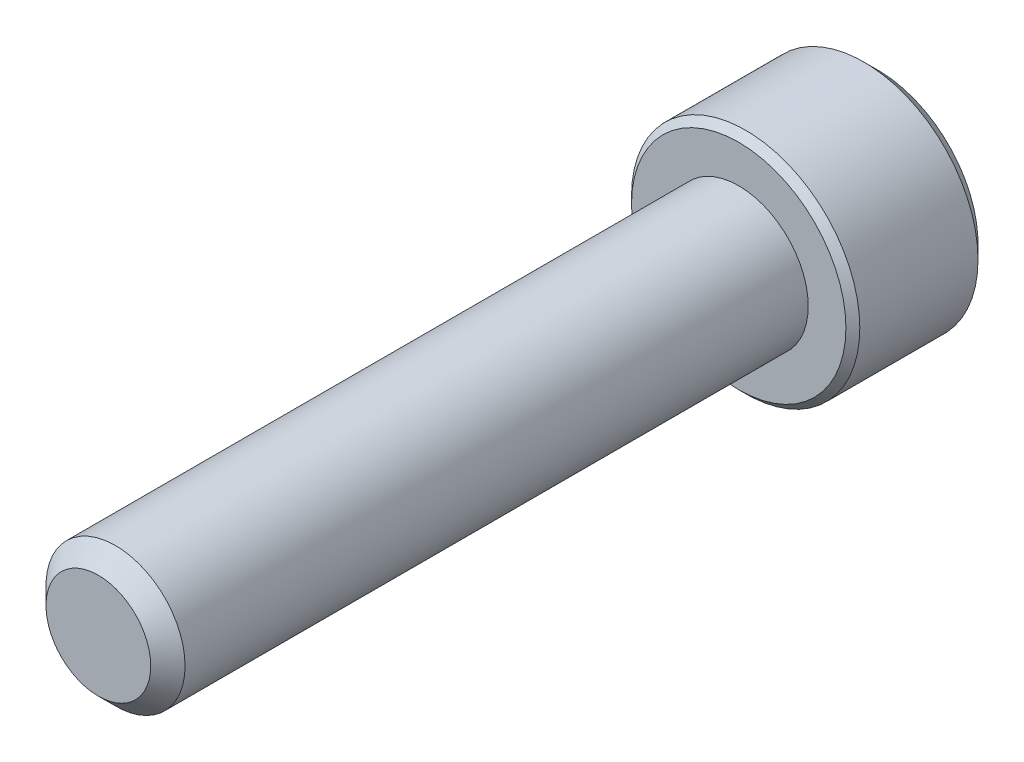
SolidWorks part; units mm, degrees
ref_plane "Front Plane" through (0, 0, 0) normal (0, 0, 1) x (1, 0, 0)
ref_plane "Top Plane" through (0, 0, 0) normal (0, 1, 0) x (1, 0, 0)
ref_plane "Right Plane" through (0, 0, 0) normal (1, 0, 0) x (0, 0, -1)
sketch "Sketch1" plane through (0, 0, 0) normal (0, 0, 1) x (1, 0, 0)
  line L0 (0, 2.413) -> (0, -2.413) construction
  circle A0 centre (0, 0) radius 2.413
  dimension "OD" = 4.826
extrude "Extrude1" add sketch "Sketch1" against normal blind 22.225
sketch "Sketch2" plane through (0, 0, 0) normal (0, 0, 1) x (1, 0, 0)
  circle A0 centre (0, 0) radius 2.413 construction
  circle A1 centre (0, 0) radius 2.413
curve "Helix/Spiral1" pitch 0.7937 height 23.0188 turns 29 parameters "pitch"=0.7937
chamfer "Chamfer3" distance 0.5953 angle 45 1 edges at (2.413, 0, 0)
sketch "Sketch3" plane through (0, 0, 0) normal (1, 0, 0) x (0, 0, -1)
  line L0 (-0.6945, 2.413) -> (-0.3969, 1.8974)
  line L1 (-0.3969, 1.8974) -> (-0.2977, 1.8974)
  line L2 (-0.2977, 1.8974) -> (0, 2.413)
  line L3 (-0.6945, 2.413) -> (0, 2.413)
  line L4 (-0.3473, 2.413) -> (-0.3473, 1.8974) construction
  line L5 (-0.5457, 2.1552) -> (-0.1488, 2.1552) construction
  line L6 (0, 2.413) -> (0, -2.413) construction
  dimension "D1" = 0.0992
  dimension "D2" = 0.3969
  dimension "D3" = 60
sweep "Cut-Sweep1" [suppressed] cut profiles "Sketch3" path "Helix/Spiral1"
sketch "Sketch6" plane through (0, 0, -22.225) normal (0, 0, -1) x (-1, 0, 0)
  circle A0 centre (0, 0) radius 3.9624
  dimension "head dia" = 7.9248
extrude "Extrude2" add sketch "Sketch6" along normal blind 4.826
sketch "Sketch7" plane through (0, 0, -27.051) normal (0, 0, -1) x (-1, 0, 0)
  line L1 (0, 2.2914) -> (-1.9844, 1.1457)
  line L2 (-1.9844, 1.1457) -> (-1.9844, -1.1457)
  line L3 (-1.9844, -1.1457) -> (0, -2.2914)
  line L4 (0, -2.2914) -> (1.9844, -1.1457)
  line L5 (1.9844, -1.1457) -> (1.9844, 1.1457)
  line L6 (1.9844, 1.1457) -> (0, 2.2914)
  circle A0 centre (0, 0) radius 1.9844 construction
  dimension "hex dia" = 3.9688
extrude "Cut-Extrude1" cut sketch "Sketch7" against normal blind 2.9766
sketch "Sketch8" plane through (0, 0, -27.051) normal (0, 0, -1) x (-1, 0, 0)
  circle A0 centre (0, 0) radius 2.2914
extrude "Cut-Extrude2" cut sketch "Sketch8" against normal blind 0.4826 draft 45
chamfer "Chamfer1" distance 0.4826 angle 45 1 edges at (-3.9624, 0, -27.051)
chamfer "Chamfer2" distance 0.2413 angle 45 1 edges at (-3.9624, 0, -22.225)
sketch "Sketch9" plane through (0, 0, 0) normal (1, 0, 0) x (0, 0, -1)
  line L0 (0, 2.413) -> (0, -2.413) construction
  line L1 (4.3656, 2.413) -> (4.3656, -2.413) construction
  line L2 (22.225, 3.9624) -> (22.225, -3.9624) construction
  line L3 (27.051, 3.9624) -> (27.051, -3.9624) construction
  line L4 (27.051, 0) -> (0, 0) construction
  dimension "D1" = 4.3656
  dimension "D2" = 4.826
  dimension "D3" = 7.9248
  dimension "D4" = 22.225
equation "\"D3@Helix/Spiral1\" = \"screw length@Extrude1\"+\"pitch@Helix/Spiral1\""
equation "\"D1@Sketch3\" = \"pitch@Helix/Spiral1\"*.125"
equation "\"D2@Sketch3\" = \"pitch@Helix/Spiral1\"*.5"
equation "\"D1@Cut-Extrude1\" = \"hex dia@Sketch7\"*.75"
equation "\"D1@Chamfer1\" = \"head depth@Extrude2\"/10"
equation "\"D1@Sketch9\" = \"pitch@Helix/Spiral1\"*5.5"
equation "\"D1@Chamfer2\" = \"D1@Chamfer1\"/2"
equation "\"D1@Cut-Extrude2\" = \"D1@Chamfer2\"*2"
equation "\"D1@Chamfer3\" = \"pitch@Helix/Spiral1\"*.750"
equation "\"D2@Sketch9\" = \"head depth@Extrude2\""
equation "\"D3@Sketch9\" = \"head dia@Sketch6\""
equation "\"D4@Sketch9\" = \"screw length@Extrude1\""
